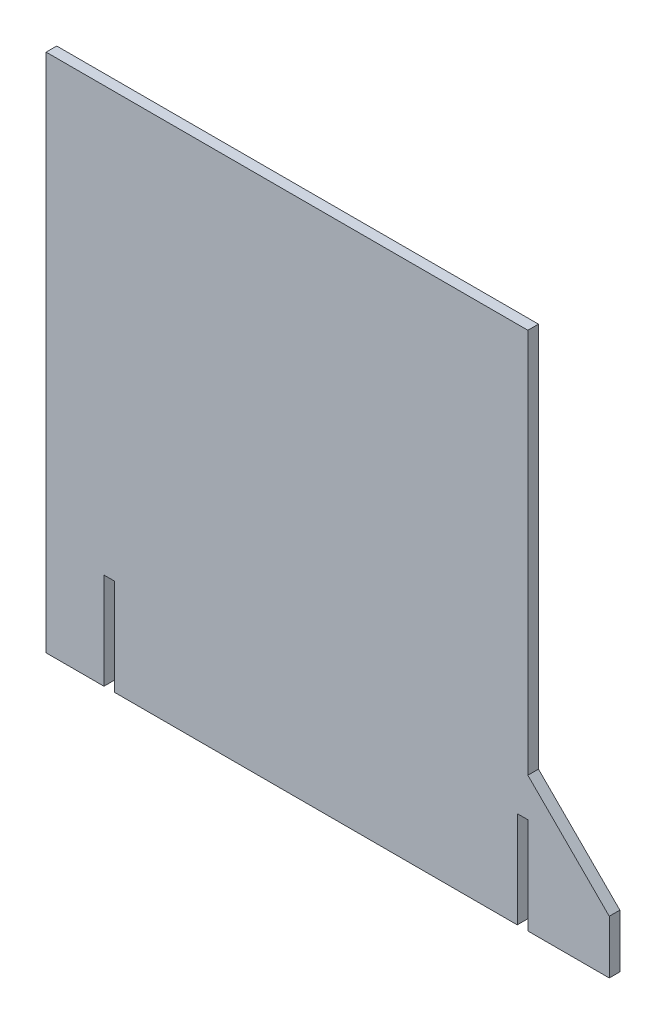
SolidWorks part; units mm, degrees
ref_plane "前基準面" through (0, 0, 0) normal (0, 0, 1) x (1, 0, 0)
ref_plane "上基準面" through (0, 0, 0) normal (0, 1, 0) x (1, 0, 0)
ref_plane "右基準面" through (0, 0, 0) normal (1, 0, 0) x (0, 0, -1)
sketch "草圖1" plane through (0, 0, 0) normal (0, 0, 1) x (1, 0, 0)
  line L0 (250, 70) -> (292.2463, 27.7537)
  line L1 (0, 0) -> (142.2463, 0)
  line L2 (0, 0) -> (0, 270)
  line L3 (0, 270) -> (250, 270)
  line L4 (250, 70) -> (250, 270)
  line L5 (292.2463, 27.7537) -> (292.2463, 0)
  line L6 (292.2463, 0) -> (142.2463, 0)
  dimension "D1" = 250
  dimension "D2" = 270
  dimension "D3" = 135
  dimension "D4" = 150
  dimension "D5" = 70
extrude "填料-伸長1" add sketch "草圖1" along normal blind 5.5
sketch "草圖3" plane through (250, 0, 0) normal (1, 0, 0) x (0, 0, -1)
  line L0 (-5.5, 70) -> (-5.5, 270) construction
  line L1 (-5.5, 290) -> (-3, 290)
  line L2 (-5.5, 290) -> (-5.5, 190)
  line L3 (-5.5, 190) -> (-3, 190)
  line L4 (-3, 193) -> (-3, 190)
  line L5 (0, 70) -> (0, 270) construction
  line L6 (0, 290) -> (-2.5, 290)
  line L7 (0, 290) -> (0, 190)
  line L8 (0, 190) -> (-2.5, 190)
  line L9 (-2.5, 193) -> (-2.5, 190)
  line L10 (-5.5, 190) -> (0, 190) construction
  line L11 (-5.5, 270) -> (0, 270) construction
  line L12 (-3, 193) -> (-2.5, 193)
  point P16 (-2.75, 193)
  dimension "D1" = 100
  dimension "D2" = 100
  dimension "D3" = 2.5
  dimension "D4" = 2.5
  dimension "D5" = 80
  dimension "D6" = 3
extrude "除料-伸長1" [suppressed] cut sketch "草圖3" against normal through all
sketch "草圖4" plane through (0, 0, 5.5) normal (0, 0, 1) x (1, 0, 0)
  line L0 (0, 0) -> (292.2463, 0) construction
  line L1 (30, 0) -> (35.5, 0)
  line L2 (30, 0) -> (30, 50)
  line L3 (30, 50) -> (35.5, 50)
  line L4 (35.5, 0) -> (35.5, 50)
  line L5 (0, 270) -> (0, 0) construction
  line L7 (244.5, 0) -> (250, 0)
  line L8 (244.5, 0) -> (244.5, 50)
  line L9 (244.5, 50) -> (250, 50)
  line L10 (250, 0) -> (250, 50)
  line L11 (250, 70) -> (250, 270) construction
  dimension "D1" = 5.5
  dimension "D2" = 50
  dimension "D3" = 30
  dimension "D4" = 50
  dimension "D5" = 5.5
extrude "除料-伸長2" cut sketch "草圖4" against normal blind 10
